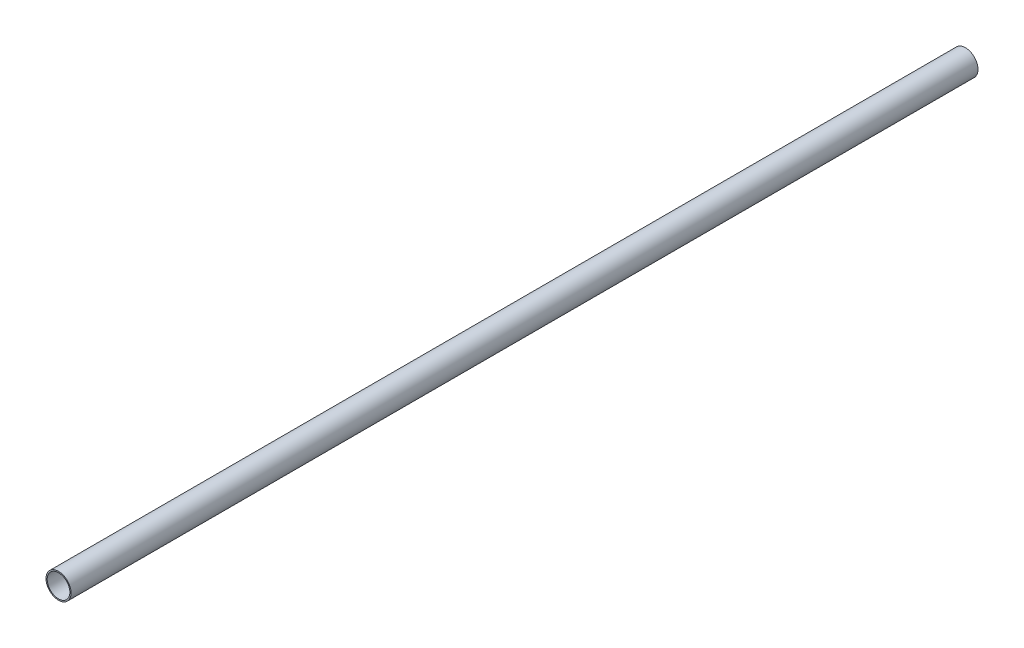
SolidWorks part; units mm, degrees
ref_plane "Front Plane" through (0, 0, 0) normal (0, 0, 1) x (1, 0, 0)
ref_plane "Top Plane" through (0, 0, 0) normal (0, 1, 0) x (1, 0, 0)
ref_plane "Right Plane" through (0, 0, 0) normal (1, 0, 0) x (0, 0, -1)
sketch "Sketch1" plane through (0, 0, 0) normal (0, 0, 1) x (1, 0, 0)
  circle A0 centre (0, 0) radius 0.375
  circle A1 centre (0, 0) radius 0.415
  dimension "D1" = 0.83
  dimension "D2" = 0.75
extrude "Boss-Extrude1" add sketch "Sketch1" along normal blind 30
